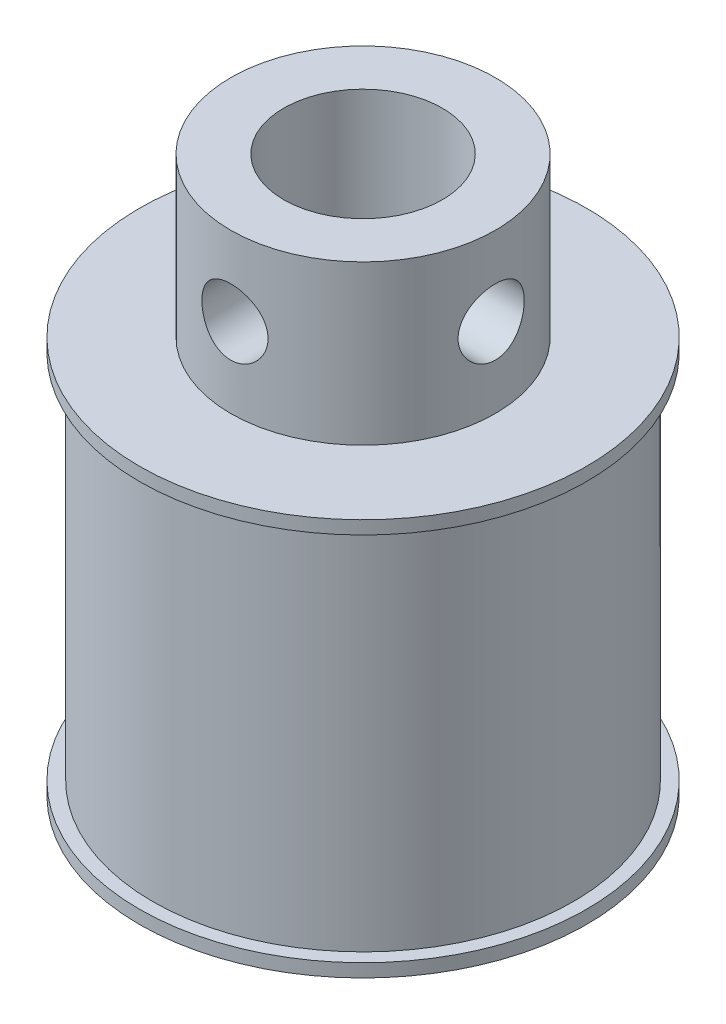
SolidWorks part; units mm, degrees
ref_plane "Alzado" through (0, 0, 0) normal (1, 0, 0) x (0, 1, 0)
ref_plane "Planta" through (0, 0, 0) normal (0, 0, 1) x (0, 1, 0)
ref_plane "Vista lateral" through (0, 0, 0) normal (0, 1, 0) x (-1, 0, 0)
sketch "Croquis1" plane through (0, 0, 0) normal (0, 1, 0) x (-1, 0, 0)
  circle A0 centre (0, 0) radius 7.95
  dimension "D1" = 15.9
extrude "Saliente-Extruir1" add sketch "Croquis1" along normal mid plane 15
sketch "Croquis2" plane through (0, 7.5, 0) normal (0, 1, 0) x (-1, 0, 0)
  circle A3 centre (0, 0) radius 8.45
  dimension "D1" = 16.9
extrude "Saliente-Extruir2" add sketch "Croquis2" against normal blind 0.5
extrude "Saliente-Extruir3" add sketch "Croquis2<2>" along normal blind 0.5 from surface starting at face at (0, -7.5, 7.95)
sketch "Croquis2<2>" plane through (0, 7.5, 0) normal (0, 1, 0) x (-1, 0, 0) same geometry as "Croquis2"
sketch "Croquis3" plane through (0, -7.5, 0) normal (0, 1, 0) x (-1, 0, 0)
  circle A0 centre (0, 0) radius 5
  dimension "D1" = 10
extrude "Saliente-Extruir4" add sketch "Croquis3" along normal blind 21
sketch "Croquis4" plane through (0, -7, 0) normal (0, 1, 0) x (-1, 0, 0)
  circle A0 centre (0, 0) radius 3
  dimension "D1" = 6
extrude "Cortar-Extruir1" cut sketch "Croquis4" against normal through all both and the other way through all
sketch "Croquis5" plane through (0, 0, 0) normal (0, 0, 1) x (0, 1, 0)
  line L4 (10.5, 5) -> (10.5, -5) construction
  line L5 (13.5, 5) -> (7.5, 5) construction
  line L9 (7.5, -5) -> (7.5, 5) construction
  line L10 (7.5, -5) -> (7.5, 5) construction
  point P10 (10.5, 0)
sketch "Croquis6" plane through (0, 0, 0) normal (1, 0, 0) x (0, 1, 0)
  point P0 (10.5, 0)
hole_wizard "Taladro roscado M32" positions "Croquis6" profile "Croquis7" tap size "M3" standard "DIN" end condition up to next
sketch "Croquis7" plane through (0, 10.5, 0) normal (0, 1, 0) x (0, 0, 1)
  line L0 (0, 0) -> (0, 5)
  line L1 (0, 5) -> (1.25, 5)
  line L2 (1.25, 5) -> (1.25, 0)
  line L5 (1.25, 0) -> (0, 0)
  line L11 (0, -6.35) -> (0, 107.95) construction
  dimension "Diámetro de perforador para roscar hasta el siguiente" = 2.5
  dimension "Profundidad de perforador para roscar hasta el siguiente" = 5
cosmetic thread "Rosca de taladro1" parameters "D2"=3
hole_wizard "Taladro roscado M31" positions "Croquis5" profile "Croquis9" tap size "M3" standard "DIN" end condition through all
sketch "Croquis9" plane through (0, 10.5, 0) normal (1, 0, 0) x (0, 1, 0)
  line L0 (0, 0) -> (0, 8.45)
  line L1 (0, 8.45) -> (1.25, 8.45)
  line L2 (1.25, 8.45) -> (1.25, 0)
  line L5 (1.25, 0) -> (0, 0)
  line L11 (0, -6.35) -> (0, 107.95) construction
  dimension "Diámetro de perforador para roscar hasta el siguiente" = 2.5
  dimension "Profundidad de perforador para roscar hasta el siguiente" = 8.45
cosmetic thread "Rosca de taladro2" parameters "D2"=3
ref_axis "Eje1" through (0, 10.5, 5) along (0, 0, -1)
ref_axis "Eje2" through (5, 10.5, 0) along (-1, 0, 0)
sketch "Croquis10" plane through (0, -7.5, 0) normal (0, -1, 0) x (1, 0, 0)
  circle A0 centre (0, 0) radius 4
  dimension "D1" = 8
extrude "Cortar-Extruir2" [suppressed] cut sketch "Croquis10" against normal through all
equation "\"Dp\"= 15.9"
equation "\"D1@Croquis1\"=\"Dp\""
equation "\"Dm\"= 10"
equation "\"De\"= \"Dp\" + 1"
equation "\"F\"= 15"
equation "\"L\"= 21"
equation "\"D1@Croquis2\"=\"De\""
equation "\"D1@Saliente-Extruir1\"=\"F\""
equation "\"D1@Saliente-Extruir4\"=\"L\""
equation "\"agujero\"= 6"
equation "\"D1@Croquis4\"=\"agujero\""
